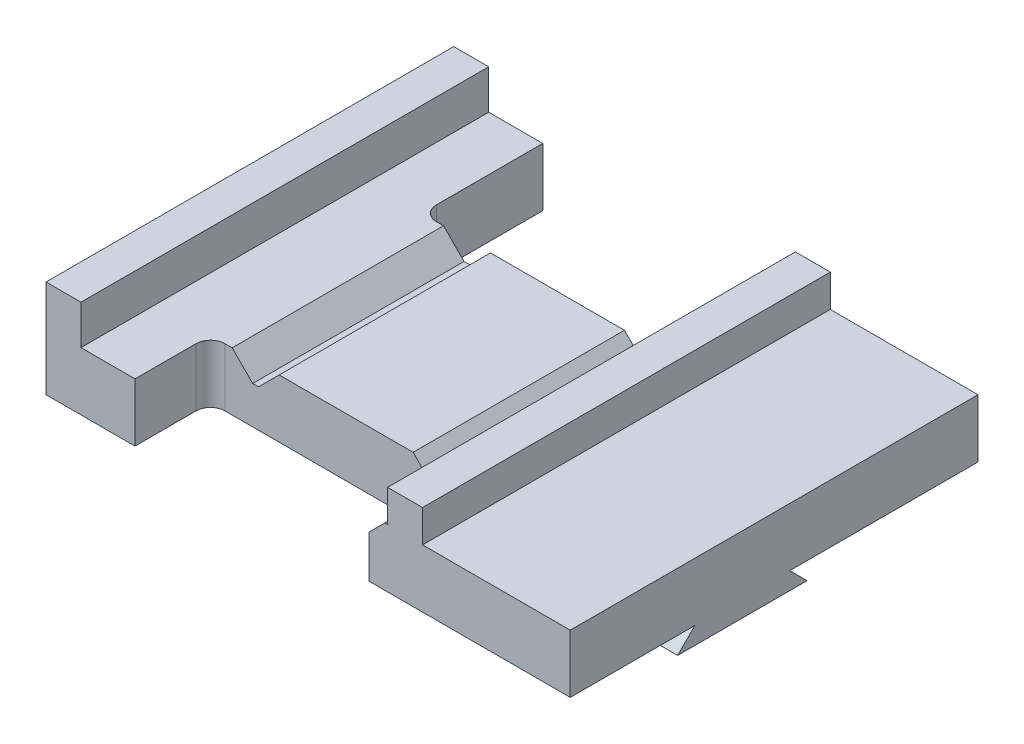
SolidWorks part; units mm, degrees
ref_plane "Front Plane" through (0, 0, 0) normal (0, 0, 1) x (1, 0, 0)
ref_plane "Top Plane" through (0, 0, 0) normal (0, 1, 0) x (1, 0, 0)
ref_plane "Right Plane" through (0, 0, 0) normal (1, 0, 0) x (0, 0, -1)
sketch "Sketch1" plane through (0, 0, 0) normal (0, 0, 1) x (1, 0, 0)
  line L0 (-151.9042, 0.4789) -> (-151.9042, 20.5906)
  line L1 (-151.9042, 20.5906) -> (-139.9042, 20.5906)
  line L2 (-139.9042, 20.5906) -> (-139.9042, 7.0711)
  line L3 (-139.9042, 7.0711) -> (-113.9042, 7.0711)
  line L4 (-113.9042, 7.0711) -> (-106.8331, 0)
  line L5 (-106.8331, 0) -> (-104.8331, 0)
  line L6 (-104.8331, 0) -> (-97.762, 7.0711)
  line L7 (-97.762, 7.0711) -> (-51.762, 7.0711)
  line L8 (-51.762, 7.0711) -> (-44.691, 0)
  line L9 (-44.691, 0) -> (-42.691, 0)
  line L10 (-42.691, 0) -> (-35.6199, 7.0711)
  line L11 (-35.6199, 7.0711) -> (-34.6199, 7.0711)
  line L12 (-34.6199, 7.0711) -> (-34.6199, 18.18)
  line L13 (-34.6199, 18.18) -> (-22.6199, 18.18)
  line L14 (-22.6199, 18.18) -> (-22.6199, 7.0711)
  line L15 (-22.6199, 7.0711) -> (28.0958, 7.0711)
  line L16 (28.0958, 7.0711) -> (28.0958, -12.9289)
  line L17 (28.0958, -12.9289) -> (-151.9042, -12.9289)
  line L18 (-151.9042, -12.9289) -> (-151.9042, 0.4789)
  dimension "D1" = 180
  dimension "D2" = 10
  dimension "D3" = 10
  dimension "D4" = 2
  dimension "D5" = 10
  dimension "D6" = 10
  dimension "D7" = 2
  dimension "D8" = 12
  dimension "D9" = 46
  dimension "D10" = 1
  dimension "D11" = 12
  dimension "D12" = 225
  dimension "D13" = 20
  dimension "D14" = 26
extrude "Boss-Extrude1" add sketch "Sketch1" along normal blind 140
sketch "Sketch2" plane through (28.0958, 0, 0) normal (1, 0, 0) x (0, 0, -1)
  line L0 (-97.1813, -12.9289) -> (-103.1351, -18.8828)
  line L1 (-140, -12.9289) -> (0, -12.9289) construction
  line L2 (-103.1351, -18.8828) -> (-58.6791, -18.8828)
  line L3 (-58.6791, -18.8828) -> (-64.6329, -12.9289)
  line L4 (-64.6329, -12.9289) -> (-97.1813, -12.9289)
  dimension "D1" = 45
  dimension "D2" = 45
extrude "Boss-Extrude2" add sketch "Sketch2" against normal blind 180
sketch "Sketch3" plane through (0, -12.9289, 0) normal (0, -1, 0) x (1, 0, 0)
  line L0 (-151.9042, 0) -> (28.0958, 0) construction
  line L1 (-121.3429, 0) -> (-41.0392, 0)
  line L2 (-121.3429, 0) -> (-121.3429, 36.5202)
  line L3 (-116.3429, 41.5202) -> (-46.0392, 41.5202)
  line L4 (-41.0392, 0) -> (-41.0392, 36.5202)
  line L5 (-151.9042, 140) -> (28.0958, 140) construction
  line L6 (-121.3429, 140) -> (-41.0392, 140)
  line L7 (-121.3429, 140) -> (-121.3429, 119.087)
  line L8 (-116.3429, 114.087) -> (-46.0392, 114.087)
  line L9 (-41.0392, 140) -> (-41.0392, 119.087)
  arc A0 (-46.0392, 41.5202) -> (-41.0392, 36.5202) centre (-46.0392, 36.5202) cw
  arc A1 (-121.3429, 36.5202) -> (-116.3429, 41.5202) centre (-116.3429, 36.5202) cw
  arc A2 (-46.0392, 114.087) -> (-41.0392, 119.087) centre (-46.0392, 119.087) ccw
  arc A3 (-121.3429, 119.087) -> (-116.3429, 114.087) centre (-116.3429, 119.087) ccw
  dimension "D1" = 5
extrude "Cut-Extrude1" cut sketch "Sketch3" against normal blind 100
